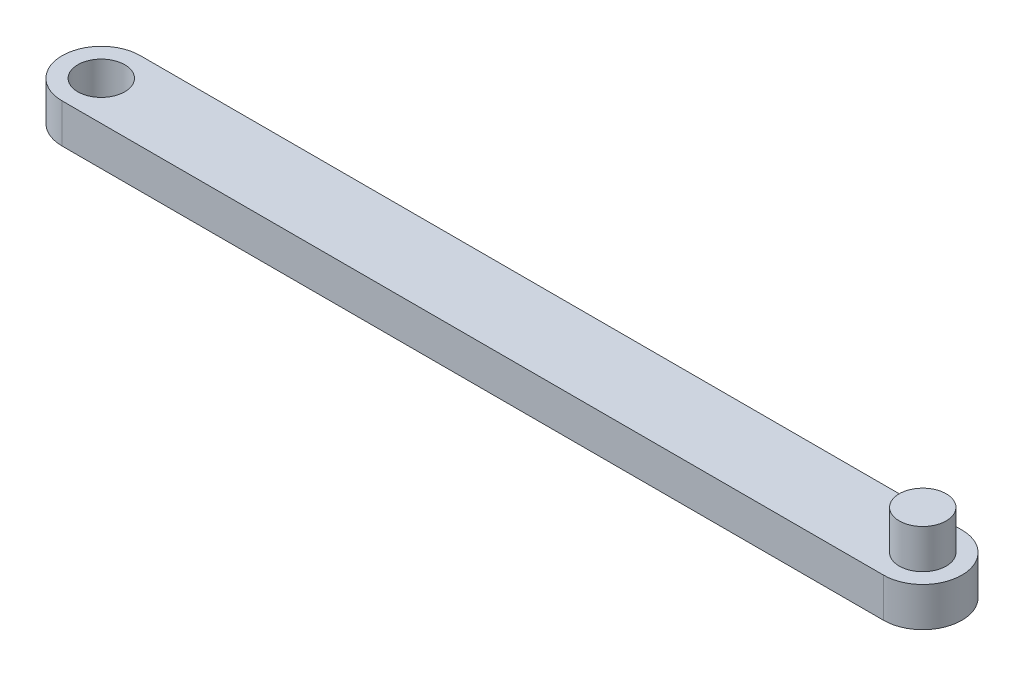
SolidWorks part; units mm, degrees
ref_plane "前视基准面" through (0, 0, 0) normal (0, 0, 1) x (1, 0, 0)
ref_plane "上视基准面" through (0, 0, 0) normal (0, 1, 0) x (1, 0, 0)
ref_plane "右视基准面" through (0, 0, 0) normal (1, 0, 0) x (0, 0, -1)
sketch "草图1" plane through (0, 0, 0) normal (0, 1, 0) x (1, 0, 0)
  line L0 (0, 0) -> (104.91, 0)
  line L2 (104.91, -10) -> (0, -10)
  arc A0 (0, 0) -> (0, -10) centre (0, -5) ccw
  arc A1 (104.91, -10) -> (104.91, 0) centre (104.91, -5) ccw
  circle A2 centre (0, -5) radius 3
  dimension "D1" = 104.91
  dimension "D2" = 10
extrude "凸台-拉伸1" add sketch "草图1" along normal blind 5
sketch "草图2" plane through (0, 5, 0) normal (0, 1, 0) x (1, 0, 0)
  circle A0 centre (104.91, -5) radius 3
extrude "凸台-拉伸2" add sketch "草图2" along normal blind 5
